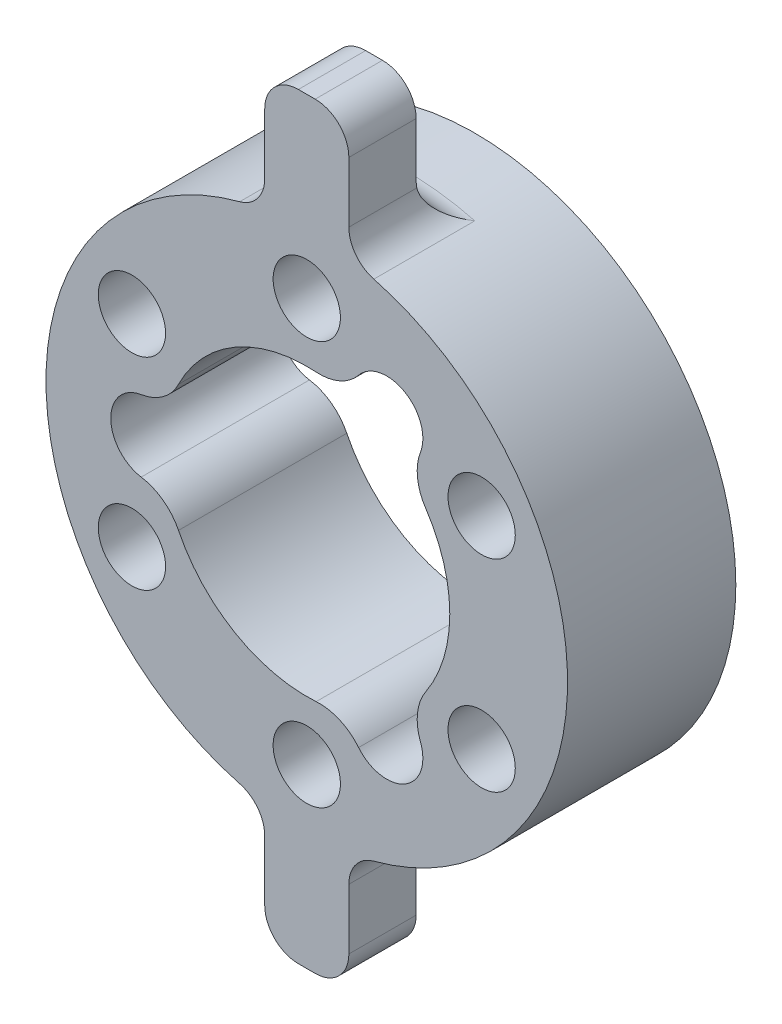
SolidWorks part; units mm, degrees
ref_plane "前视基准面" through (0, 0, 0) normal (0, 0, 1) x (1, 0, 0)
ref_plane "上视基准面" through (0, 0, 0) normal (0, 1, 0) x (1, 0, 0)
ref_plane "右视基准面" through (0, 0, 0) normal (1, 0, 0) x (0, 0, -1)
other "Configuration Table"
sketch "草图1" plane through (0, 0, 0) normal (0, 0, 1) x (1, 0, 0)
  line L0 (0, 12) -> (0, 0) construction
  line L1 (0, 0) -> (4.75, 8.2272) construction
  circle A0 centre (0, 12) radius 2
  circle A1 centre (10.3923, 6) radius 2
  circle A2 centre (10.3923, -6) radius 2
  circle A3 centre (0, -12) radius 2
  circle A4 centre (-10.3923, -6) radius 2
  circle A5 centre (-10.3923, 6) radius 2
  circle A6 centre (4.75, 8.2272) radius 2.15
  circle A7 centre (4.75, -8.2272) radius 2.15
  circle A8 centre (-9.5, 0) radius 2.15
  circle A9 centre (0, 0) radius 15.5
  circle A10 centre (0, 0) radius 8.5
  point P15 (0, 0)
  point P23 (0, 0)
  dimension "D1" = 4
  dimension "D4" = 4.3
  dimension "D8" = 31
  dimension "D9" = 17
  dimension "D2" = 12
  dimension "D5" = 30
  dimension "D6" = 9.5
  dimension "D3" = 6
  dimension "D7" = 3
extrude "凸台-拉伸1" add sketch "草图1" along normal blind 10 contours A9 A10 A6 A7 A8 A0 A1 A2 A3 A4 A5 region at (-15.0616, 0, 0)
fillet "圆角1" radius 3 6 edges at (-8.3093, -1.7902, 5) (2.6043, -8.0912, 5) (5.705, -6.301, 5) (5.705, 6.301, 5) (2.6043, 8.0912, 5) (-8.3093, 1.7902, 5)
sketch "草图2" plane through (0, 0, 10) normal (0, 0, 1) x (1, 0, 0)
  line L1 (2.5, 22.5) -> (2.5, -22.5)
  line L2 (2.5, 22.5) -> (-2.5, 22.5)
  line L3 (2.5, -22.5) -> (-2.5, -22.5)
  line L4 (-2.5, 22.5) -> (-2.5, -22.5)
  line L5 (2.5, 22.5) -> (-2.5, -22.5) construction
  line L6 (2.5, -22.5) -> (-2.5, 22.5) construction
  line L7 (0, 12) -> (0, -12) construction
  circle A0 centre (10.3923, 6) radius 2 construction
  circle A1 centre (-10.3923, -6) radius 2 construction
  circle A2 centre (10.3923, 6) radius 2 construction
  circle A3 centre (-10.3923, -6) radius 2 construction
  circle A4 centre (10.3923, -6) radius 2 construction
  circle A5 centre (0, 0) radius 15.5
  circle A6 centre (0, 0) radius 15.5
  circle A7 centre (-10.3923, 6) radius 2 construction
  circle A8 centre (10.3923, -6) radius 2
  circle A9 centre (-10.3923, 6) radius 2
  circle A10 centre (0, -12) radius 2 construction
  circle A11 centre (0, 12) radius 2 construction
  circle A12 centre (0, -12) radius 2
  circle A13 centre (0, 12) radius 2
  point P7 (0, 0)
  circle M25 centre (0, 0) radius 15.5
  dimension "D2" = 5
  dimension "D3" = 45
  dimension "D1" = 0
extrude "凸台-拉伸2" add sketch "草图2" against normal blind 4 contours L4 L3 L1 M25 | L2 L4 L1 M25 region at (0, 18.966, 10) region at (0, -18.966, 10)
fillet "圆角2" radius 2 8 edges at (2.5, -15.2971, 8) (2.5, -22.5, 8) (-2.5, -22.5, 8) (-2.5, 15.2971, 8) (-2.5, 22.5, 8) (2.5, 22.5, 8) (2.5, 15.2971, 8) (-2.5, -15.2971, 8)
fillet "圆角3" radius 2 2 edges at (0, -15.5, 6) (0, 15.5, 6)
